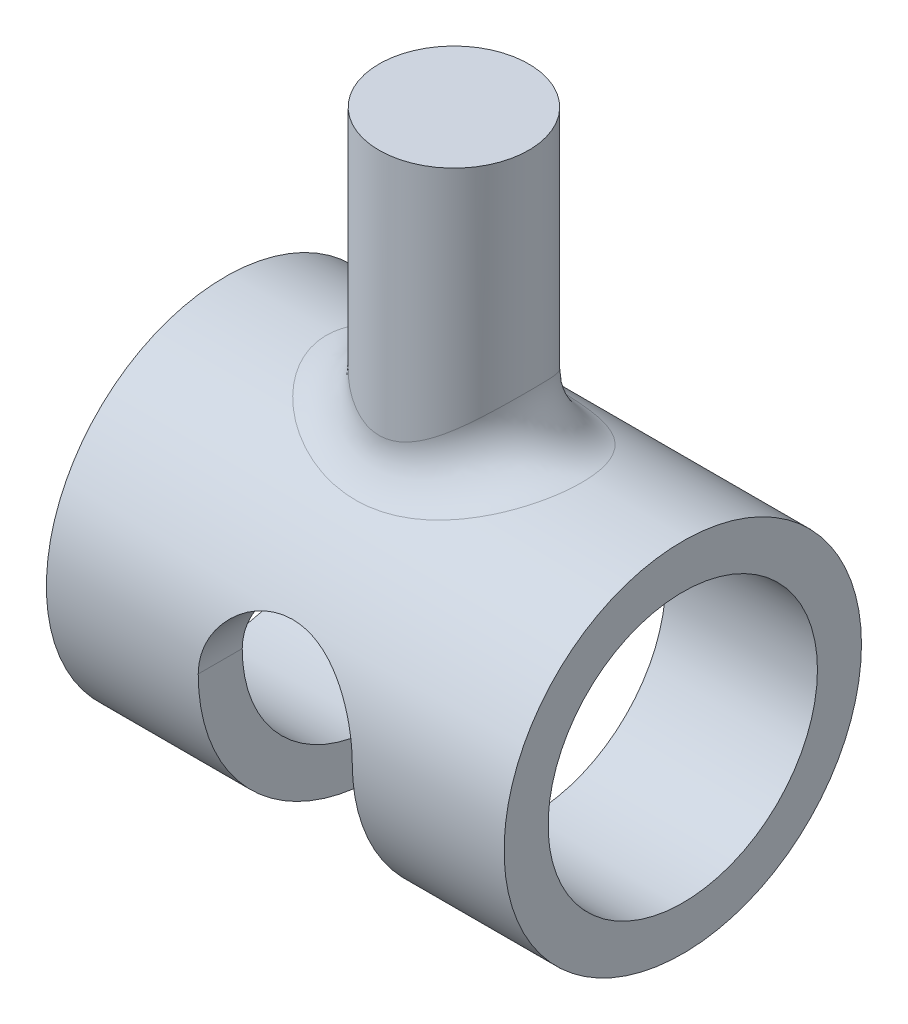
SolidWorks part; units mm, degrees
ref_plane "Front" through (0, 0, 0) normal (0, 0, 1) x (1, 0, 0)
ref_plane "Top" through (0, 0, 0) normal (0, 1, 0) x (1, 0, 0)
ref_plane "Right" through (0, 0, 0) normal (1, 0, 0) x (0, 0, -1)
ref_axis "Axis1" through (0, 0, 0) along (1, 0, 0)
sketch "Sketch1" plane through (0, 0, 0) normal (1, 0, 0) x (0, 0, -1)
  circle A0 centre (0, 0) radius 7.5 construction
  circle A1 centre (0, 0) radius 7.65
  circle A2 centre (0, 0) radius 10.15
  dimension "D1" = 15
  dimension "D2" = 0.15
  dimension "D3" = 2.5
extrude "Boss-Extrude1" add sketch "Sketch1" along normal mid plane 26
sketch "Sketch2" plane through (0, 0, 0) normal (0, 1, 0) x (1, 0, 0)
  line L1 (-4.375, -10.15) -> (4.375, -10.15)
  line L2 (-4.375, -10.15) -> (-4.375, -7.65)
  line L3 (-4.375, -7.65) -> (4.375, -7.65)
  line L4 (4.375, -10.15) -> (4.375, -7.65)
  point P9 (0, -7.65)
  dimension "D1" = 8.75
revolve "Cut-Revolve1" cut sketch "Sketch2" angle 180 about axis through (0, 0, 0) along (1, 0, 0)
ref_plane "Plane1" through (0, 25, 0) normal (0, 1, 0) x (1, 0, 0)
sketch "Sketch4" plane through (0, 25, 0) normal (0, 1, 0) x (1, 0, 0)
  circle A0 centre (0, 0) radius 4.25
  dimension "D1" = 8.5
extrude "Boss-Extrude2" add sketch "Sketch4" against normal up to surface (15.7826 mm away) up to face at (0, -5.075, 0)
fillet "Fillet1" radius 3 1 edges at (-0.5949, 9.2366, -4.2082)
sketch "Sketch5" plane through (0, 0, 0) normal (0, 0, 1) x (1, 0, 0)
  line L0 (-4.375, 0) -> (4.375, 0) construction
  circle A0 centre (0, 0) radius 4.375
extrude "Cut-Extrude1" cut sketch "Sketch5" against normal through all both and the other way through all
